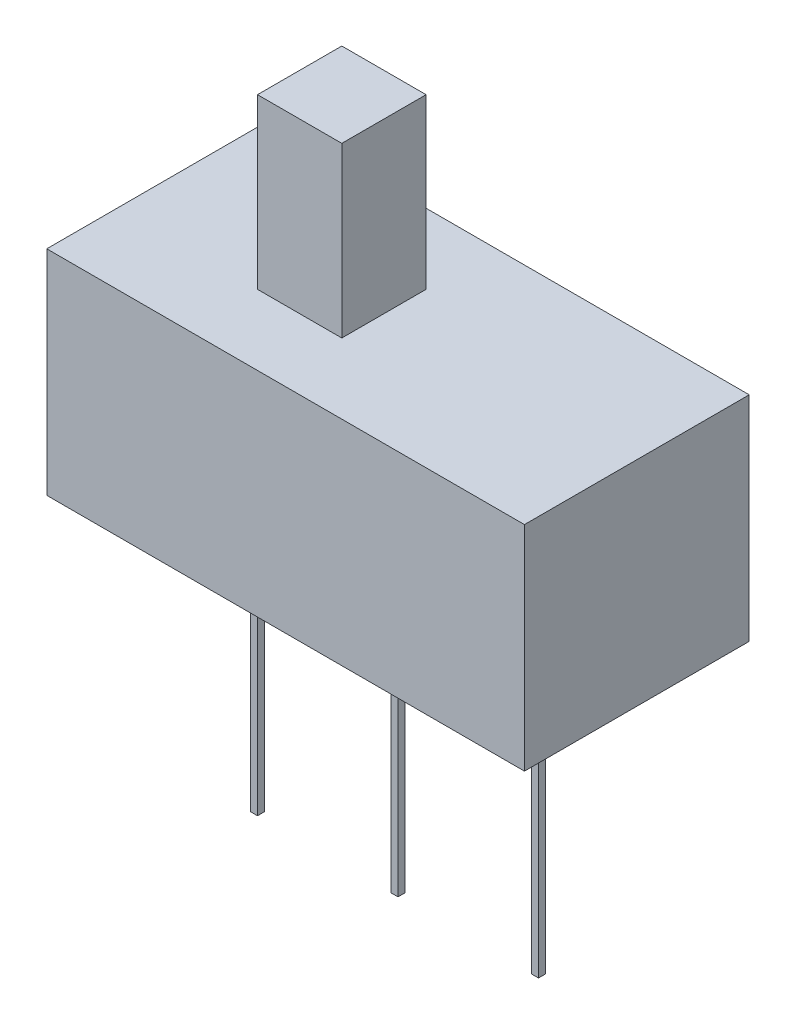
SolidWorks part; units mm, degrees
material "Alumina"
ref_plane "Front" through (0, 0, 0) normal (0, 0, 1) x (1, 0, 0)
ref_plane "Top" through (0, 0, 0) normal (0, 1, 0) x (1, 0, 0)
ref_plane "Right" through (0, 0, 0) normal (1, 0, 0) x (0, 0, -1)
sketch "Sketch1" plane through (0, 0, 0) normal (0, 0, 1) x (1, 0, 0)
  line L1 (-4.25, 1.9) -> (4.25, 1.9)
  line L2 (-4.25, 1.9) -> (-4.25, -1.9)
  line L3 (-4.25, -1.9) -> (4.25, -1.9)
  line L4 (4.25, 1.9) -> (4.25, -1.9)
  line L5 (-4.25, 1.9) -> (4.25, -1.9) construction
  line L6 (-4.25, -1.9) -> (4.25, 1.9) construction
  point P0 (0, 0)
  dimension "D1" = 8.5
  dimension "D2" = 3.8
extrude "Boss-Extrude1" add sketch "Sketch1" along normal mid plane 4
sketch "Sketch2" plane through (0, 1.9, 0) normal (0, 1, 0) x (1, 0, 0)
  line L0 (-4.25, -2) -> (-4.25, 2) construction
  line L1 (-1.75, 0.75) -> (-0.25, 0.75)
  line L2 (-1.75, 0.75) -> (-1.75, -0.75)
  line L3 (-1.75, -0.75) -> (-0.25, -0.75)
  line L4 (-0.25, 0.75) -> (-0.25, -0.75)
  line L5 (-1.75, 0.75) -> (-0.25, -0.75) construction
  line L6 (-1.75, -0.75) -> (-0.25, 0.75) construction
  point P0 (-1, 0)
  dimension "D1" = 1.5
  dimension "D2" = 4
extrude "Boss-Extrude2" add sketch "Sketch2" along normal blind 3
sketch "Sketch3" plane through (0, -1.9, 0) normal (0, -1, 0) x (1, 0, 0)
  line L1 (-0.0625, 0.0625) -> (0.0625, 0.0625)
  line L2 (-0.0625, 0.0625) -> (-0.0625, -0.0625)
  line L3 (-0.0625, -0.0625) -> (0.0625, -0.0625)
  line L4 (0.0625, 0.0625) -> (0.0625, -0.0625)
  line L5 (-0.0625, 0.0625) -> (0.0625, -0.0625) construction
  line L6 (-0.0625, -0.0625) -> (0.0625, 0.0625) construction
  line L7 (-2.5625, 0.0625) -> (-2.4375, 0.0625)
  line L8 (-2.5625, 0.0625) -> (-2.5625, -0.0625)
  line L9 (-2.5625, -0.0625) -> (-2.4375, -0.0625)
  line L10 (-2.4375, 0.0625) -> (-2.4375, -0.0625)
  line L11 (-2.5625, 0.0625) -> (-2.4375, -0.0625) construction
  line L12 (-2.5625, -0.0625) -> (-2.4375, 0.0625) construction
  line L13 (2.4375, 0.0625) -> (2.5625, 0.0625)
  line L14 (2.4375, 0.0625) -> (2.4375, -0.0625)
  line L15 (2.4375, -0.0625) -> (2.5625, -0.0625)
  line L16 (2.5625, 0.0625) -> (2.5625, -0.0625)
  line L17 (2.4375, 0.0625) -> (2.5625, -0.0625) construction
  line L18 (2.4375, -0.0625) -> (2.5625, 0.0625) construction
  point P0 (0, 0)
  point P5 (2.5, 0)
  point P8 (-2.5, 0)
  dimension "D1" = 0.125
  dimension "D2" = 2.5
  dimension "D3" = 2.5
extrude "Boss-Extrude3" add sketch "Sketch3" along normal blind 5
